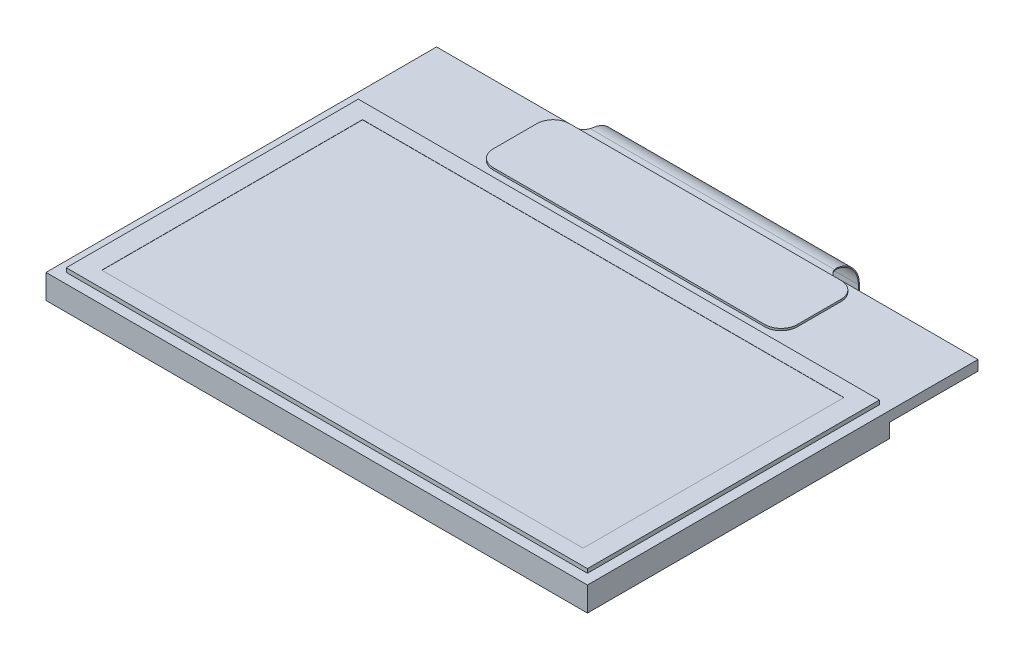
SolidWorks part; units mm, degrees
ref_plane "Front Plane" through (0, 0, 0) normal (0, 0, 1) x (1, 0, 0)
ref_plane "Top Plane" through (0, 0, 0) normal (0, 1, 0) x (1, 0, 0)
ref_plane "Right Plane" through (0, 0, 0) normal (1, 0, 0) x (0, 0, -1)
sketch "Sketch1" plane through (0, 0, 0) normal (0, 1, 0) x (1, 0, 0)
  line L1 (-13.35, 9.63) -> (13.35, 9.63)
  line L2 (-13.35, 9.63) -> (-13.35, -9.63)
  line L3 (-13.35, -9.63) -> (13.35, -9.63)
  line L4 (13.35, 9.63) -> (13.35, -9.63)
  line L5 (-13.35, 9.63) -> (13.35, -9.63) construction
  line L6 (-13.35, -9.63) -> (13.35, 9.63) construction
  point P0 (0, 0)
  dimension "D1" = 26.7
  dimension "D2" = 19.26
extrude "Boss-Extrude1" add sketch "Sketch1" along normal blind 0.5
sketch "Sketch2" plane through (0, 0, 0) normal (0, -1, 0) x (1, 0, 0)
  line L0 (13.35, 9.63) -> (13.35, -9.63) construction
  line L1 (-13.35, 9.63) -> (13.35, 9.63)
  line L2 (-13.35, 9.63) -> (-13.35, -5.27)
  line L3 (-13.35, -5.27) -> (13.35, -5.27)
  line L4 (13.35, 9.63) -> (13.35, -5.27)
  dimension "D1" = 14.9
extrude "Boss-Extrude2" add sketch "Sketch2" along normal blind 0.7
sketch "Sketch3" plane through (0, 0.5, 0) normal (0, 1, 0) x (1, 0, 0)
  line L0 (-13.35, -9.63) -> (13.35, -9.63) construction
  line L1 (12.85, -9.13) -> (-12.85, -9.13)
  line L2 (12.85, -9.13) -> (12.85, 5.27)
  line L3 (12.85, 5.27) -> (-12.85, 5.27)
  line L4 (-12.85, -9.13) -> (-12.85, 5.27)
  line L5 (13.35, -9.63) -> (13.35, 9.63) construction
  line L6 (-13.35, 9.63) -> (-13.35, -9.63) construction
  dimension "D1" = 14.9
  dimension "D2" = 0.5
  dimension "D3" = 0.5
  dimension "D4" = 0.5
extrude "Boss-Extrude3" add sketch "Sketch3" along normal blind 0.2
sketch "Sketch4" plane through (0, 0.7, 0) normal (0, 1, 0) x (1, 0, 0)
  line L0 (0, 5.27) -> (0, -9.13) construction
  line L1 (12.85, 5.27) -> (-12.85, 5.27) construction
  line L2 (-12.85, -9.13) -> (12.85, -9.13) construction
  line L4 (-11.87, 4.5) -> (11.87, 4.5)
  line L5 (-11.87, 4.5) -> (-11.87, -8.36)
  line L6 (-11.87, -8.36) -> (11.87, -8.36)
  line L7 (11.87, 4.5) -> (11.87, -8.36)
  line L8 (-11.87, 4.5) -> (11.87, -8.36) construction
  line L9 (-11.87, -8.36) -> (11.87, 4.5) construction
  point P6 (0, -1.93)
  dimension "D1" = 23.74
  dimension "D2" = 12.86
extrude "Cut-Extrude1" cut sketch "Sketch4" against normal blind 0.01
sketch "Sketch5" plane through (0, 0.5, 0) normal (0, 1, 0) x (1, 0, 0)
  line L0 (0, 0) -> (0, 9.63) construction
  line L1 (6.7, 5.77) -> (-6.7, 5.77)
  line L2 (7.5, 6.57) -> (7.5, 8.73)
  line L3 (6.7, 9.53) -> (-6.7, 9.53)
  line L4 (-7.5, 6.57) -> (-7.5, 8.73)
  line L5 (13.35, 9.63) -> (-13.35, 9.63) construction
  line L6 (12.85, 5.27) -> (-12.85, 5.27) construction
  line L7 (6, 9.53) -> (6, 14.63) construction
  line L8 (6, 14.63) -> (11, 17.63) construction
  line L9 (11, 17.63) -> (11, 21.63) construction
  line L10 (11, 21.63) -> (-11, 21.63) construction
  line L11 (-11, 17.63) -> (-11, 21.63) construction
  line L12 (-6, 14.63) -> (-11, 17.63) construction
  line L13 (-6, 9.53) -> (-6, 14.63) construction
  line L14 (-13.35, -9.63) -> (13.35, -9.63) construction
  line L15 (417.513, 199.2663) -> (48.8463, 199.2663) construction
  arc A0 (7.5, 8.73) -> (6.7, 9.53) centre (6.7, 8.73) ccw
  arc A1 (6.7, 5.77) -> (7.5, 6.57) centre (6.7, 6.57) ccw
  arc A2 (-6.7, 5.77) -> (-7.5, 6.57) centre (-6.7, 6.57) cw
  arc A3 (-6.7, 9.53) -> (-7.5, 8.73) centre (-6.7, 8.73) ccw
  point P17 (0, 21.63)
  point P28 (7.5, 5.77)
  point P31 (-7.5, 5.77)
  dimension "D9" = 0.8
  dimension "D1" = 15
  dimension "D2" = 0.5
  dimension "D3" = 0.1
  dimension "D4" = 12
  dimension "D5" = 22
  dimension "D6" = 31.26
  dimension "D7" = 4
  dimension "D8" = 5
extrude "Boss-Extrude4" add sketch "Sketch5" along normal blind 0.1
sketch "Sketch6" plane through (0, 0, 0) normal (1, 0, 0) x (0, 0, -1)
  line L0 (9.53, 0.55) -> (9.88, 0.55)
  line L1 (11.13, -0.7) -> (11.13, -1.15)
  line L2 (9.88, -2.4) -> (9.43, -2.4)
  line L3 (5.27, -0.7) -> (-9.63, -0.7) construction
  line L4 (9.53, 0.55) -> (9.53, 0.5)
  line L5 (9.53, 0.5) -> (9.88, 0.5)
  line L6 (11.08, -0.7) -> (11.08, -1.15)
  line L7 (9.88, -2.35) -> (9.43, -2.35)
  line L8 (9.43, -2.35) -> (9.43, -2.4)
  line L9 (9.63, 0.5) -> (9.63, 0) construction
  line L10 (9.53, 0.6) -> (9.53, 0.5) construction
  line L11 (-9.63, 0.5) -> (9.63, 0.5) construction
  arc A0 (11.08, -1.15) -> (9.88, -2.35) centre (9.88, -1.15) cw
  arc A1 (9.88, 0.5) -> (11.08, -0.7) centre (9.88, -0.7) cw
  arc A2 (11.13, -1.15) -> (9.88, -2.4) centre (9.88, -1.15) cw
  arc A3 (9.88, 0.55) -> (11.13, -0.7) centre (9.88, -0.7) cw
  point P22 (9.53, 0.5)
  point P25 (0, 0)
  point P26 (9.53, 0.5721)
  point P27 (9.53, 0.5)
  dimension "D7" = 1.2
  dimension "D8" = 1.25
  dimension "D1" = 1.7
  dimension "D2" = 1.5
  dimension "D3" = 0.05
  dimension "D4" = 0.05
  dimension "D5" = 1.7
  dimension "D6" = 0.05
extrude "Boss-Extrude5" add sketch "Sketch6" along normal mid plane 12
sketch "Sketch7" plane through (0, -2.4, 0) normal (0, -1, 0) x (1, 0, 0)
  line L0 (-81.7283, -215.6457) -> (-450.395, -215.6457) construction
  line L1 (0, 0) -> (0, -18.729) construction
  line L2 (-11, -2.43) -> (11, -2.43)
  line L3 (11, -2.43) -> (11, -6.43)
  line L4 (11, -6.43) -> (6, -9.13)
  line L5 (6, -9.13) -> (6, -9.43)
  line L6 (6, -9.43) -> (0, -9.43)
  line L7 (6, -9.43) -> (-6, -9.43) construction
  line L8 (-11, -2.43) -> (-11, -6.43)
  line L9 (-11, -6.43) -> (-6, -9.13)
  line L10 (-6, -9.13) -> (-6, -9.43)
  line L11 (-6, -9.43) -> (0, -9.43)
  circle A0 centre (-8, -7.18) radius 0.4
  circle A1 centre (8, -7.18) radius 0.4
  point P8 (0, -2.43)
  dimension "D7" = 0.8
  dimension "D1" = 7
  dimension "D2" = 4
  dimension "D3" = 0.3
  dimension "D4" = 22
  dimension "D5" = 8
  dimension "D6" = 4.75
extrude "Boss-Extrude6" add sketch "Sketch7" against normal up to surface (0.05 mm away) up to face at (0, -2.35, -9.655)
sketch "Sketch9" plane through (0, -2.4, 0) normal (0, -1, 0) x (1, 0, 0)
  line L0 (11, -2.43) -> (-11, -2.43) construction
  line L1 (-11, -2.43) -> (11, -2.43)
  line L2 (-11, -2.43) -> (-11, -4.43)
  line L3 (-11, -4.43) -> (11, -4.43)
  line L4 (11, -2.43) -> (11, -4.43)
  line L5 (11, -6.43) -> (11, -2.43) construction
  line L6 (-11, -2.43) -> (-11, -6.43) construction
  point P8 (-11, -5.0005)
  dimension "D1" = 2
extrude "Cut-Extrude2" cut sketch "Sketch9" against normal blind 0.01
sketch "Sketch8" plane through (0, -2.4, 0) normal (0, -1, 0) x (1, 0, 0)
  line L0 (11, -2.43) -> (-11, -2.43) construction
  line L1 (-10.35, -2.43) -> (-9.95, -2.43)
  line L2 (-10.35, -2.43) -> (-10.35, -4.43)
  line L3 (-10.35, -4.43) -> (-9.95, -4.43)
  line L4 (-9.95, -2.43) -> (-9.95, -4.43)
  line L5 (-10.15, -4.43) -> (-10.15, -2.43) construction
  line L6 (-11, -4.43) -> (-11, -6.43) construction
  line L7 (-9.65, -2.43) -> (-9.65, -4.43)
  line L8 (-9.65, -2.43) -> (-9.25, -2.43)
  line L9 (-9.25, -2.43) -> (-9.25, -4.43)
  line L10 (-9.65, -4.43) -> (-9.25, -4.43)
  line L11 (-8.95, -2.43) -> (-8.95, -4.43)
  line L12 (-8.95, -2.43) -> (-8.55, -2.43)
  line L13 (-8.55, -2.43) -> (-8.55, -4.43)
  line L14 (-8.95, -4.43) -> (-8.55, -4.43)
  line L15 (-8.25, -2.43) -> (-8.25, -4.43)
  line L16 (-8.25, -2.43) -> (-7.85, -2.43)
  line L17 (-7.85, -2.43) -> (-7.85, -4.43)
  line L18 (-8.25, -4.43) -> (-7.85, -4.43)
  line L19 (-7.55, -2.43) -> (-7.55, -4.43)
  line L20 (-7.55, -2.43) -> (-7.15, -2.43)
  line L21 (-7.15, -2.43) -> (-7.15, -4.43)
  line L22 (-7.55, -4.43) -> (-7.15, -4.43)
  line L23 (-6.85, -2.43) -> (-6.85, -4.43)
  line L24 (-6.85, -2.43) -> (-6.45, -2.43)
  line L25 (-6.45, -2.43) -> (-6.45, -4.43)
  line L26 (-6.85, -4.43) -> (-6.45, -4.43)
  line L27 (-6.15, -2.43) -> (-6.15, -4.43)
  line L28 (-6.15, -2.43) -> (-5.75, -2.43)
  line L29 (-5.75, -2.43) -> (-5.75, -4.43)
  line L30 (-6.15, -4.43) -> (-5.75, -4.43)
  line L31 (-5.45, -2.43) -> (-5.45, -4.43)
  line L32 (-5.45, -2.43) -> (-5.05, -2.43)
  line L33 (-5.05, -2.43) -> (-5.05, -4.43)
  line L34 (-5.45, -4.43) -> (-5.05, -4.43)
  line L35 (-4.75, -2.43) -> (-4.75, -4.43)
  line L36 (-4.75, -2.43) -> (-4.35, -2.43)
  line L37 (-4.35, -2.43) -> (-4.35, -4.43)
  line L38 (-4.75, -4.43) -> (-4.35, -4.43)
  line L39 (-4.05, -2.43) -> (-4.05, -4.43)
  line L40 (-4.05, -2.43) -> (-3.65, -2.43)
  line L41 (-3.65, -2.43) -> (-3.65, -4.43)
  line L42 (-4.05, -4.43) -> (-3.65, -4.43)
  line L43 (-3.35, -2.43) -> (-3.35, -4.43)
  line L44 (-3.35, -2.43) -> (-2.95, -2.43)
  line L45 (-2.95, -2.43) -> (-2.95, -4.43)
  line L46 (-3.35, -4.43) -> (-2.95, -4.43)
  line L47 (-2.65, -2.43) -> (-2.65, -4.43)
  line L48 (-2.65, -2.43) -> (-2.25, -2.43)
  line L49 (-2.25, -2.43) -> (-2.25, -4.43)
  line L50 (-2.65, -4.43) -> (-2.25, -4.43)
  line L51 (-1.95, -2.43) -> (-1.95, -4.43)
  line L52 (-1.95, -2.43) -> (-1.55, -2.43)
  line L53 (-1.55, -2.43) -> (-1.55, -4.43)
  line L54 (-1.95, -4.43) -> (-1.55, -4.43)
  line L55 (-1.25, -2.43) -> (-1.25, -4.43)
  line L56 (-1.25, -2.43) -> (-0.85, -2.43)
  line L57 (-0.85, -2.43) -> (-0.85, -4.43)
  line L58 (-1.25, -4.43) -> (-0.85, -4.43)
  line L59 (-0.55, -2.43) -> (-0.55, -4.43)
  line L60 (-0.55, -2.43) -> (-0.15, -2.43)
  line L61 (-0.15, -2.43) -> (-0.15, -4.43)
  line L62 (-0.55, -4.43) -> (-0.15, -4.43)
  line L63 (0.15, -2.43) -> (0.15, -4.43)
  line L64 (0.15, -2.43) -> (0.55, -2.43)
  line L65 (0.55, -2.43) -> (0.55, -4.43)
  line L66 (0.15, -4.43) -> (0.55, -4.43)
  line L67 (0.85, -2.43) -> (0.85, -4.43)
  line L68 (0.85, -2.43) -> (1.25, -2.43)
  line L69 (1.25, -2.43) -> (1.25, -4.43)
  line L70 (0.85, -4.43) -> (1.25, -4.43)
  line L71 (1.55, -2.43) -> (1.55, -4.43)
  line L72 (1.55, -2.43) -> (1.95, -2.43)
  line L73 (1.95, -2.43) -> (1.95, -4.43)
  line L74 (1.55, -4.43) -> (1.95, -4.43)
  line L75 (2.25, -2.43) -> (2.25, -4.43)
  line L76 (2.25, -2.43) -> (2.65, -2.43)
  line L77 (2.65, -2.43) -> (2.65, -4.43)
  line L78 (2.25, -4.43) -> (2.65, -4.43)
  line L79 (2.95, -2.43) -> (2.95, -4.43)
  line L80 (2.95, -2.43) -> (3.35, -2.43)
  line L81 (3.35, -2.43) -> (3.35, -4.43)
  line L82 (2.95, -4.43) -> (3.35, -4.43)
  line L83 (3.65, -2.43) -> (3.65, -4.43)
  line L84 (3.65, -2.43) -> (4.05, -2.43)
  line L85 (4.05, -2.43) -> (4.05, -4.43)
  line L86 (3.65, -4.43) -> (4.05, -4.43)
  line L87 (4.35, -2.43) -> (4.35, -4.43)
  line L88 (4.35, -2.43) -> (4.75, -2.43)
  line L89 (4.75, -2.43) -> (4.75, -4.43)
  line L90 (4.35, -4.43) -> (4.75, -4.43)
  line L91 (5.05, -2.43) -> (5.05, -4.43)
  line L92 (5.05, -2.43) -> (5.45, -2.43)
  line L93 (5.45, -2.43) -> (5.45, -4.43)
  line L94 (5.05, -4.43) -> (5.45, -4.43)
  line L95 (5.75, -2.43) -> (5.75, -4.43)
  line L96 (5.75, -2.43) -> (6.15, -2.43)
  line L97 (6.15, -2.43) -> (6.15, -4.43)
  line L98 (5.75, -4.43) -> (6.15, -4.43)
  line L99 (6.45, -2.43) -> (6.45, -4.43)
  line L100 (6.45, -2.43) -> (6.85, -2.43)
  line L101 (6.85, -2.43) -> (6.85, -4.43)
  line L102 (6.45, -4.43) -> (6.85, -4.43)
  line L103 (7.15, -2.43) -> (7.15, -4.43)
  line L104 (7.15, -2.43) -> (7.55, -2.43)
  line L105 (7.55, -2.43) -> (7.55, -4.43)
  line L106 (7.15, -4.43) -> (7.55, -4.43)
  line L107 (7.85, -2.43) -> (7.85, -4.43)
  line L108 (7.85, -2.43) -> (8.25, -2.43)
  line L109 (8.25, -2.43) -> (8.25, -4.43)
  line L110 (7.85, -4.43) -> (8.25, -4.43)
  line L111 (8.55, -2.43) -> (8.55, -4.43)
  line L112 (8.55, -2.43) -> (8.95, -2.43)
  line L113 (8.95, -2.43) -> (8.95, -4.43)
  line L114 (8.55, -4.43) -> (8.95, -4.43)
  line L115 (9.25, -2.43) -> (9.25, -4.43)
  line L116 (9.25, -2.43) -> (9.65, -2.43)
  line L117 (9.65, -2.43) -> (9.65, -4.43)
  line L118 (9.25, -4.43) -> (9.65, -4.43)
  line L119 (9.95, -2.43) -> (9.95, -4.43)
  line L120 (9.95, -2.43) -> (10.35, -2.43)
  line L121 (10.35, -2.43) -> (10.35, -4.43)
  line L122 (9.95, -4.43) -> (10.35, -4.43)
  dimension "D1" = 0.85
  dimension "D2" = 0.4
  dimension "D3" = 2
  dimension "D4" = 30
extrude "Boss-Extrude7" add sketch "Sketch8" against normal mid plane 0.02
fillet "Fillet1" radius 0.5 8 edges at (6, 0.525, -9.53) (-6, 0.525, -9.53) (-11, -2.375, -6.43) (-6, -2.375, -9.13) (6, -2.375, -9.13) (11, -2.375, -6.43) (11, -2.37, -2.43) (-11, -2.37, -2.43)
